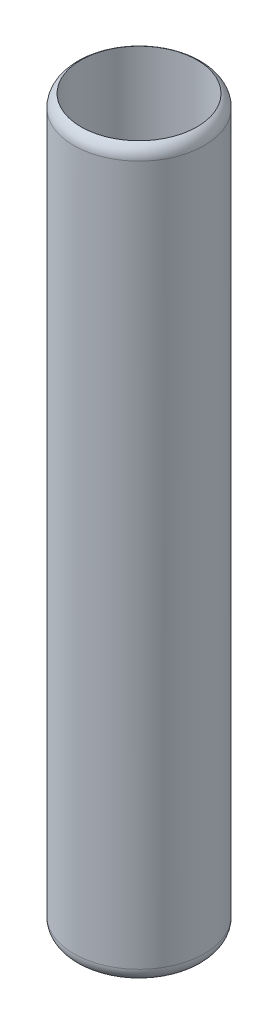
SolidWorks part; units mm, degrees
ref_plane "Alzado" through (0, 0, 0) normal (0, 0, 1) x (1, 0, 0)
ref_plane "Planta" through (0, 0, 0) normal (0, 1, 0) x (1, 0, 0)
ref_plane "Vista lateral" through (0, 0, 0) normal (1, 0, 0) x (0, 0, -1)
sketch "Sketch1" plane through (0, 0, 0) normal (0, 1, 0) x (1, 0, 0)
  circle A0 centre (0, 0) radius 4.5
  dimension "D1" = 9
extrude "Boss-Extrude1" add sketch "Sketch1" along normal blind 50
sketch "Sketch2" plane through (0, 50, 0) normal (0, 1, 0) x (1, 0, 0)
  circle A0 centre (0, 0) radius 4
  circle A1 centre (0, 0) radius 4.5 construction
  dimension "D1" = 0.5
extrude "Cut-Extrude1" cut sketch "Sketch2" against normal blind 50
fillet "Fillet2" radius 1 2 edges at (0, 0, 4.5) (0, 50, 4.5)
